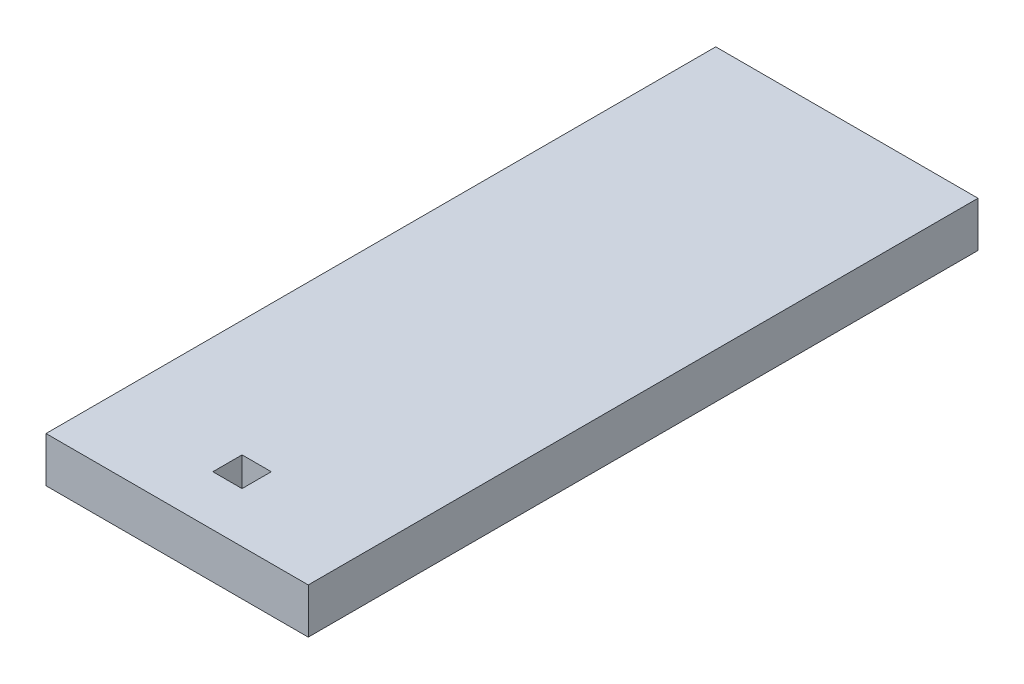
SolidWorks part; units mm, degrees
ref_plane "Front Plane" through (0, 0, 0) normal (0, 0, 1) x (1, 0, 0)
ref_plane "Top Plane" through (0, 0, 0) normal (0, 1, 0) x (1, 0, 0)
ref_plane "Right Plane" through (0, 0, 0) normal (1, 0, 0) x (0, 0, -1)
sketch "Sketch1" plane through (0, 0, 0) normal (0, 1, 0) x (1, 0, 0)
  line L0 (0, 23.495) -> (0, 0) construction
  line L1 (-9.2, 23.495) -> (9.2, 23.495)
  line L2 (-9.2, 23.495) -> (-9.2, -23.495)
  line L3 (-9.2, -23.495) -> (9.2, -23.495)
  line L4 (9.2, 23.495) -> (9.2, -23.495)
  line L5 (0, -17.9142) -> (0, 0) construction
  line L6 (-1.025, -17.9142) -> (1.025, -17.9142)
  line L7 (-1.025, -17.9142) -> (-1.025, -19.9642)
  line L8 (-1.025, -19.9642) -> (1.025, -19.9642)
  line L9 (1.025, -17.9142) -> (1.025, -19.9642)
  line L11 (-9.2, 23.495) -> (-12.375, 23.495)
  line L12 (-9.2, 23.495) -> (-9.2, -23.495)
  line L13 (-9.2, -23.495) -> (-12.375, -23.495)
  line L14 (-12.375, 23.495) -> (-12.375, -23.495)
  point P14 (9.2, 0)
  dimension "D1" = 18.4
  dimension "D2" = 46.99
  dimension "D3" = 3.5308
  dimension "D4" = 2.05
  dimension "D5" = 3.175
extrude "Boss-Extrude1" add sketch "Sketch1" along normal blind 3.175 contours L4 L1 L2 L3 L6 L9 L8 L7 | L11 L14 L13 L2 region at (0, 0, -0.0925) region at (-10.7875, 0, 0)
sketch "Sketch2" plane through (0, 3.175, 0) normal (0, 1, 0) x (1, 0, 0)
  line L0 (-12.375, -23.495) -> (9.2, -23.495) construction
  line L1 (-12.375, 23.495) -> (-9.2, 23.495)
  line L2 (-12.375, 23.495) -> (-12.375, -23.495)
  line L3 (-12.375, -23.495) -> (-9.2, -23.495)
  line L4 (-9.2, 23.495) -> (-9.2, -23.495)
  dimension "D1" = 3.175
extrude "Cut-Extrude1" cut sketch "Sketch2" against normal through all
equation "\"bottomThickness\"= .220in"
equation "\"wallThickness\"= .125in"
equation "\"D1@Sketch2\"=\"wallThickness\""
equation "\"D1@Boss-Extrude1\"=\"wallThickness\""
